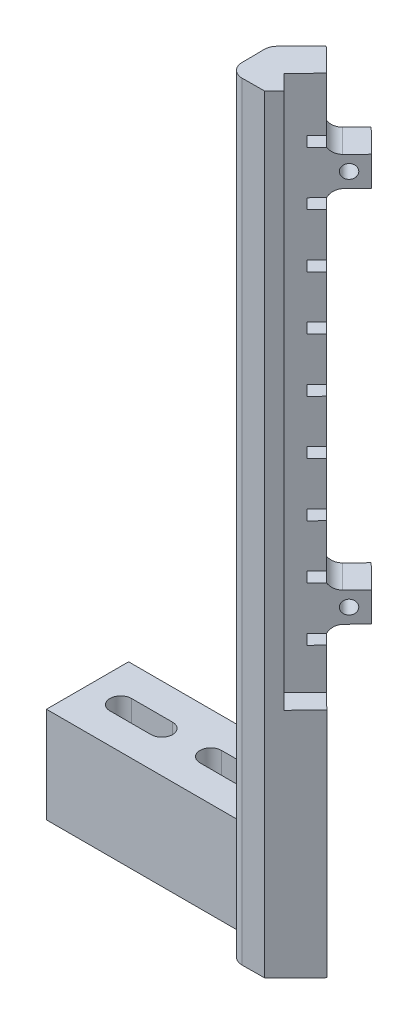
SolidWorks part; units mm, degrees
ref_plane "Front Plane" through (0, 0, 0) normal (0, 0, 1) x (1, 0, 0)
ref_plane "Top Plane" through (0, 0, 0) normal (0, 1, 0) x (1, 0, 0)
ref_plane "Right Plane" through (0, 0, 0) normal (1, 0, 0) x (0, 0, -1)
sketch "Sketch1" plane through (0, 0, 0) normal (0, 0, 1) x (1, 0, 0)
  line L0 (0, 0) -> (48.26, 0)
  line L6 (0, 0) -> (0, 17.78)
  line L10 (0, 17.78) -> (48.26, 17.78)
  line L11 (48.26, 0) -> (48.26, 17.78)
  dimension "D1" = 48.26
  dimension "D2" = 17.78
extrude "Boss-Extrude1" add sketch "Sketch1" against normal blind 15.24
sketch "Sketch3" plane through (0, 17.78, 0) normal (0, 1, 0) x (1, 0, 0)
  line L19 (0, 7.4477) -> (48.26, 7.62) construction
  line L22 (48.26, 15.24) -> (48.26, 0) construction
  line L25 (0, 15.24) -> (0, 0) construction
  line L26 (38.861, 2.4556) -> (38.9315, -0.0668)
  line L30 (38.861, 2.4556) -> (48.26, 11.9897)
  line L31 (52.6607, 7.6514) -> (44.5872, -0.5382)
  line L32 (48.26, 11.9897) -> (52.6607, 7.6514)
  line L33 (47.4358, -3.3463) -> (44.5872, -0.5382)
  line L34 (45.6526, -5.1551) -> (47.4358, -3.3463)
  line L35 (38.9681, -5.2029) -> (45.6526, -5.1551)
  line L36 (38.9315, -0.0668) -> (38.9681, -5.2029)
  line L38 (51.3672, 0.6416) -> (47.4358, -3.3463)
  line L39 (48.5187, 3.4498) -> (51.3672, 0.6416)
  point P0 (0, 0)
  point P2 (0, 0)
  point P6 (0, 0)
  line M1 (0, 0) -> (48.26, 0)
  line M2 (48.26, 0) -> (48.26, 15.24)
sketch "Sketch4" plane through (0, 17.78, 0) normal (0, 1, 0) x (1, 0, 0)
  line L0 (30.48, 7.62) -> (22.86, 7.62) construction
  line L1 (30.48, 5.62) -> (22.86, 5.62)
  line L2 (30.48, 9.62) -> (22.86, 9.62)
  line L3 (13.78, 7.62) -> (6.16, 7.62) construction
  line L4 (13.78, 5.62) -> (6.16, 5.62)
  line L5 (13.78, 9.62) -> (6.16, 9.62)
  line L6 (48.26, 0) -> (0, 0) construction
  line L7 (48.26, 15.24) -> (48.26, 0) construction
  arc A0 (30.48, 5.62) -> (30.48, 9.62) centre (30.48, 7.62) ccw
  arc A1 (22.86, 9.62) -> (22.86, 5.62) centre (22.86, 7.62) ccw
  arc A2 (13.78, 5.62) -> (13.78, 9.62) centre (13.78, 7.62) ccw
  arc A3 (6.16, 9.62) -> (6.16, 5.62) centre (6.16, 7.62) ccw
  point P2 (26.67, 7.62)
  point P7 (9.97, 7.62)
  point P14 (32.48, 7.62)
  point P16 (4.16, 7.62)
  point P18 (15.78, 7.62)
  point P19 (20.86, 7.62)
  dimension "D1" = 4
  dimension "D2" = 17.78
  dimension "D3" = 7.62
  dimension "D4" = 7.62
  dimension "D5" = 5.08
extrude "Cut-Extrude2" cut sketch "Sketch4" against normal through all
ref_plane "Plane2" through (0, 0, -7.62) normal (0, 0, 1) x (1, 0, 0)
extrude "Boss-Extrude7" add sketch "Sketch3" along normal blind 124.72
extrude "Boss-Extrude10" add sketch "Sketch3<15>" against normal through all contours M2 | L32 L31 M2 | L26 L36 L35 L34 L33 L31 M1 | L39 L31 L33 L38 M2 M1 region at (42.5565, 17.78, 2.7065) region at (49.7269, 17.78, -7.6095) region at (48.1974, 17.78, 0.2393)
sketch "Sketch3<15>" plane through (0, 17.78, 0) normal (0, 1, 0) x (1, 0, 0) same geometry as "Sketch3"
ref_plane "Plane3" through (22.881, 0, 22.5566) normal (0.7121, 0, 0.702) x (0.702, 0, -0.7121)
extrude "Boss-Extrude11" add sketch "Sketch3<16>" along normal blind 25.22 contours L39 L31 L33 L38 M2 M1 | L31 M2 M1 region at (48.1974, 17.78, 0.2393) region at (47.2126, 17.78, -1.0625)
sketch "Sketch3<16>" plane through (0, 17.78, 0) normal (0, 1, 0) x (1, 0, 0) same geometry as "Sketch3"
hole_wizard "Tapped Hole for M2.5x0.45 Helicoil1" positions "Sketch6" profile "Sketch8" tap size "M2.5x0.45" standard "Helicoil® Metric" end condition up to next
sketch "Sketch6" plane through (72.1766, -14.555, -27.448) normal (0.7121, 0, 0.702) x (0.702, 0, -0.7121)
  line L4 (-39.2988, 157.055) -> (-39.2988, 57.555) construction
  line L8 (-33.6988, 57.555) -> (-39.2988, 57.555) construction
  point P0 (-30.7488, 71.255)
  point P7 (-30.7488, 141.2549)
  dimension "D1" = 13.7
  dimension "D2" = 8.55
  dimension "D3" = 69.9999
sketch "Sketch8" plane through (50.5897, 56.7, -5.5506) normal (0, 1, 0) x (0.702, 0, -0.7121)
  line L0 (0, 0) -> (0, 6.1796)
  line L1 (0, 6.1796) -> (1.275, 6.1796)
  line L2 (1.275, 6.1796) -> (1.275, 0)
  line L5 (1.275, 0) -> (0, 0)
  line L11 (0, -6.35) -> (0, 107.95) construction
  dimension "Thru Tap Drill Dia." = 2.55
  dimension "Thru Tap Drill Depth" = 6.1796
cosmetic thread "Hole Thread5" parameters "D1"=3.7998, "D2"=3.55
cosmetic thread "Hole Thread6" parameters "D1"=3.7998, "D2"=3.55
sketch "Sketch10" plane through (22.881, 0, 22.5566) normal (0.7121, 0, 0.702) x (0.702, 0, -0.7121)
  line L3 (33.9188, 140.5) -> (30.9188, 140.5)
  line L13 (30.9188, 140.5) -> (30.9188, 99.5492)
  line L46 (33.9188, 43) -> (30.9188, 43)
  line L47 (30.9188, 43) -> (30.9188, 99.5492)
  line L48 (30.9188, 142.5) -> (30.9188, 43) construction
  line L49 (36.5188, 43) -> (33.9188, 43)
  line L50 (30.9188, 142.5) -> (30.9188, 43) construction
  line L51 (36.5188, 43) -> (30.9188, 43) construction
  line L52 (36.5188, 43) -> (36.5188, 0)
  line L53 (36.5188, 50.6) -> (36.5188, 43)
  line L54 (36.5188, 50.6) -> (33.9188, 50.6)
  line L55 (33.9188, 50.6) -> (33.9188, 52.5)
  line L56 (33.9188, 52.5) -> (36.5188, 52.5)
  line L57 (42.4188, 53.95) -> (38.7876, 53.95)
  line L58 (42.4188, 53.95) -> (42.4188, 59.45)
  line L59 (42.4188, 59.45) -> (38.623, 59.45)
  line L60 (36.5188, 60.6) -> (33.9188, 60.6)
  line L61 (33.9188, 60.6) -> (33.9188, 62.5)
  line L62 (33.9188, 62.5) -> (36.5188, 62.5)
  line L63 (33.9188, 82.5) -> (36.5188, 82.5)
  line L64 (33.9188, 80.6) -> (33.9188, 82.5)
  line L65 (36.5188, 80.6) -> (33.9188, 80.6)
  line L66 (36.5188, 80.6) -> (36.5188, 72.5)
  line L67 (33.9188, 70.6) -> (33.9188, 72.5)
  line L68 (33.9188, 72.5) -> (36.5188, 72.5)
  line L69 (36.5188, 70.6) -> (33.9188, 70.6)
  line L70 (36.5188, 70.6) -> (36.5188, 62.5)
  line L71 (33.9188, 110.6) -> (33.9188, 112.5)
  line L72 (36.5188, 110.6) -> (33.9188, 110.6)
  line L73 (36.5188, 110.6) -> (36.5188, 102.5)
  line L74 (33.9188, 102.5) -> (36.5188, 102.5)
  line L75 (33.9188, 100.6) -> (33.9188, 102.5)
  line L76 (36.5188, 100.6) -> (33.9188, 100.6)
  line L77 (36.5188, 100.6) -> (36.5188, 92.5)
  line L78 (33.9188, 92.5) -> (36.5188, 92.5)
  line L79 (33.9188, 90.6) -> (33.9188, 92.5)
  line L80 (36.5188, 90.6) -> (33.9188, 90.6)
  line L81 (36.5188, 90.6) -> (36.5188, 82.5)
  line L82 (36.5188, 142.5) -> (33.9188, 142.5)
  line L83 (33.9188, 140.5) -> (33.9188, 142.5)
  line L84 (33.9188, 132.5) -> (36.5188, 132.5)
  line L85 (36.5188, 142.5) -> (36.5188, 132.5)
  line L86 (33.9188, 130.6) -> (33.9188, 132.5)
  line L87 (36.5188, 130.6) -> (33.9188, 130.6)
  line L88 (42.4188, 129.45) -> (38.623, 129.45)
  line L89 (42.4188, 123.95) -> (42.4188, 129.45)
  line L90 (42.4188, 123.95) -> (38.7876, 123.95)
  line L91 (33.9188, 122.5) -> (36.5188, 122.5)
  line L92 (33.9188, 120.6) -> (33.9188, 122.5)
  line L93 (36.5188, 120.6) -> (33.9188, 120.6)
  line L94 (36.5188, 120.6) -> (36.5188, 112.5)
  line L95 (33.9188, 112.5) -> (36.5188, 112.5)
  line L96 (36.5188, 142.5) -> (44.7334, 142.5)
  line L97 (44.7334, 0) -> (44.7334, 142.5)
  line L99 (36.5188, 0) -> (44.7334, 0)
  line L100 (42.4188, 142.5) -> (42.4188, 0) construction
  line L101 (42.4188, 43) -> (42.4188, 53.95)
  arc A4 (36.5188, 52.5) -> (38.7876, 53.95) centre (38.7876, 51.45) cw
  arc A5 (38.623, 59.45) -> (36.5188, 60.6) centre (38.623, 61.95) cw
  arc A6 (38.623, 129.45) -> (36.5188, 130.6) centre (38.623, 131.95) cw
  arc A7 (36.5188, 122.5) -> (38.7876, 123.95) centre (38.7876, 121.45) cw
  point P0 (0, 0)
  point P8 (0, 0)
  point P10 (0, 0)
extrude "Cut-Extrude3" cut sketch "Sketch10" against normal through all contours A4 L56 L55 L54 L53 L101 L57 | A7 L91 L92 L93 L94 L95 L71 L72 L73 L74 L75 L76 L77 L78 L79 L80 L81 L63 L64 L65 L66 L68 L67 L69 L70 L62 L61 L60 A5 L59 L90 | A6 L88 L96 L85 L84 L86 L87 | L3 L83 region at (51.3082, 70.8224, -6.2795)
fillet "Fillet1" radius 2.54 1 edges at (38.9681, 71.25, 5.2029)
fillet "Fillet2" radius 2.54 1 edges at (38.861, 80.14, -2.4556)
